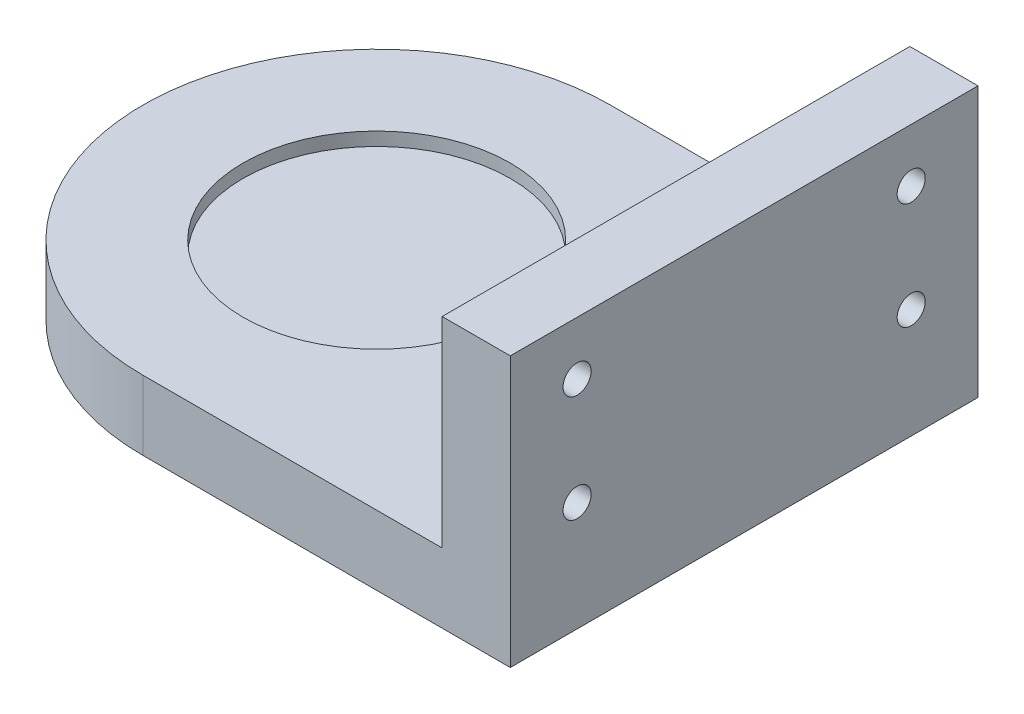
SolidWorks part; units mm, degrees
ref_plane "正面" through (0, 0, 0) normal (0, 0, 1) x (1, 0, 0)
ref_plane "平面" through (0, 0, 0) normal (0, 1, 0) x (1, 0, 0)
ref_plane "右側面" through (0, 0, 0) normal (1, 0, 0) x (0, 0, -1)
sketch "ｽｹｯﾁ1" plane through (0, 0, 0) normal (0, 1, 0) x (1, 0, 0)
  line L0 (0, 98.7597) -> (0, -97.6803) construction
  line L1 (0, 35) -> (55, 35)
  line L2 (55, 35) -> (55, -35)
  line L3 (55, -35) -> (0, -35)
  arc A0 (0, 35) -> (0, -35) centre (0, 0) ccw
  dimension "D1" = 55
  dimension "D2" = 70
extrude "押し出し1" add sketch "ｽｹｯﾁ1" against normal blind 10.4
sketch "ｽｹｯﾁ2" plane through (0, 0, 0) normal (0, -1, 0) x (-1, 0, 0)
  line L0 (-55, 35) -> (0, 35) construction
  line L1 (-55, -35) -> (-44.8, -35)
  line L2 (-55, -35) -> (-55, 35)
  line L3 (-55, 35) -> (-44.8, 35)
  line L4 (-44.8, -35) -> (-44.8, 35)
  dimension "D1" = 10.2
extrude "押し出し2" add sketch "ｽｹｯﾁ2" against normal blind 30
sketch "ｽｹｯﾁ3" plane through (55, 0, 0) normal (1, 0, 0) x (0, 0, -1)
  line L0 (0, 0) -> (0, 30) construction
  line L1 (35, 30) -> (-35, 30) construction
  line L2 (25, 22) -> (25, 6) construction
  circle A0 centre (25, 22) radius 2.1
  circle A1 centre (25, 6) radius 2.1
  circle A2 centre (-25, 6) radius 2.1
  circle A3 centre (-25, 22) radius 2.1
  dimension "D1" = 4.2
  dimension "D2" = 4.2
  dimension "D3" = 8
  dimension "D5" = 24
  dimension "D4" = 25
extrude "押し出し3" cut sketch "ｽｹｯﾁ3" against normal through all
sketch "ｽｹｯﾁ4" plane through (0, 0, 0) normal (0, 1, 0) x (1, 0, 0)
  circle A0 centre (0, 0) radius 20
  dimension "D1" = 40
extrude "押し出し4" cut sketch "ｽｹｯﾁ4" against normal blind 2
ref_axis "軸1" through (0, -2, 0) along (0, 1, 0)
